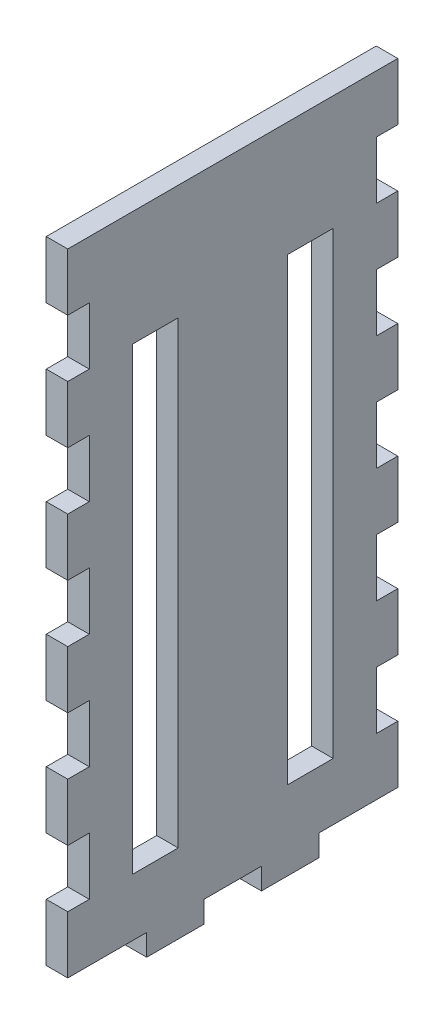
SolidWorks part; units mm, degrees
ref_plane "Front Plane" through (0, 0, 0) normal (0, 0, 1) x (1, 0, 0)
ref_plane "Top Plane" through (0, 0, 0) normal (0, 1, 0) x (1, 0, 0)
ref_plane "Right Plane" through (0, 0, 0) normal (1, 0, 0) x (0, 0, -1)
sketch "Sketch1" plane through (0, 0, 0) normal (1, 0, 0) x (0, 0, -1)
  line L1 (-63.5, -139.7) -> (63.5, -139.7)
  line L2 (-63.5, -139.7) -> (-63.5, 139.7)
  line L3 (-63.5, 139.7) -> (63.5, 139.7)
  line L4 (63.5, -139.7) -> (63.5, 139.7)
  line L5 (-63.5, -139.7) -> (63.5, 139.7) construction
  line L6 (-63.5, 139.7) -> (63.5, -139.7) construction
  point P0 (0, 0)
  dimension "D1" = 127
  dimension "D2" = 279.4
extrude "Boss-Extrude1" add sketch "Sketch1" along normal blind 9.525
sketch "Sketch2" plane through (0, 0, 63.5) normal (0, 0, 1) x (1, 0, 0)
  line L0 (0, 139.7) -> (0, -139.7) construction
  line L1 (0, 139.7) -> (9.525, 139.7)
  line L2 (0, 139.7) -> (0, 114.3)
  line L3 (0, 114.3) -> (9.525, 114.3)
  line L4 (9.525, 139.7) -> (9.525, 114.3)
  line L5 (0, -69.85) -> (0, 69.85) construction
  line L6 (9.525, 139.7) -> (9.525, -139.7) construction
  line L7 (9.525, 139.7) -> (0, 139.7) construction
  dimension "D1" = 25.4
  dimension "D2" = 0
extrude "Boss-Extrude2" add sketch "Sketch2" along normal blind 9.525
pattern_linear "LPattern1" count 6 spacing 50.8 along (0, -1, 0) of "Boss-Extrude2"
mirror "Mirror1" about plane through (0, 0, 0) normal (0, 0, 1) of "LPattern1"
sketch "Sketch3" plane through (0, -139.7, 0) normal (0, -1, 0) x (1, 0, 0)
  line L0 (0, 73.025) -> (0, -73.025) construction
  line L1 (0, 38.1) -> (9.525, 38.1)
  line L2 (0, 38.1) -> (0, 12.7)
  line L3 (0, 12.7) -> (9.525, 12.7)
  line L4 (9.525, 38.1) -> (9.525, 12.7)
  line L5 (9.525, 73.025) -> (9.525, -73.025) construction
  line L6 (0, 73.025) -> (9.525, 73.025) construction
  dimension "D1" = 34.925
  dimension "D2" = 25.4
extrude "Boss-Extrude3" add sketch "Sketch3" along normal blind 9.525
pattern_linear "LPattern2" count 2 spacing 50.8 along (0, 0, -1) of "Boss-Extrude3"
sketch "Sketch4" plane through (9.525, 0, 0) normal (1, 0, 0) x (0, 0, -1)
  line L1 (-44.45, -114.3) -> (-24.13, -114.3)
  line L3 (-44.45, 88.9) -> (-24.13, 88.9)
  line L5 (-73.025, -139.7) -> (-38.1, -139.7) construction
  line L6 (-73.025, 88.9) -> (-63.5, 88.9) construction
  line L7 (-24.13, -114.3) -> (-24.13, 88.9)
  line L8 (-44.45, -114.3) -> (-44.45, 88.9)
  line L9 (0, -139.7) -> (0, 139.7) construction
  line L10 (-12.7, -139.7) -> (12.7, -139.7) construction
  line L11 (73.025, 139.7) -> (-73.025, 139.7) construction
  point P10 (-68.2625, 88.9)
  dimension "D1" = 24.13
  dimension "D2" = 20.32
  dimension "D3" = 25.4
  dimension "D4" = 0
extrude "Cut-Extrude1" cut sketch "Sketch4" against normal blind 9.525
mirror "Mirror2" about plane through (0, 0, 0) normal (0, 0, 1) of "Cut-Extrude1"
sketch "Sketch5" plane through (0, 0, 0) normal (-1, 0, 0) x (0, 0, 1)
  circle A0 centre (-1.775, 53.4971) radius 2.5 construction
  circle A1 centre (-1.775, 53.4971) radius 2.5
  circle A2 centre (-1.775, 34.9971) radius 2.5 construction
  circle A3 centre (-1.775, 34.9971) radius 2.5
  circle A4 centre (1.775, 19.4611) radius 2.5 construction
  circle A5 centre (1.775, 19.4611) radius 2.5
  circle A6 centre (1.775, 0.9611) radius 2.5 construction
  circle A7 centre (1.775, 0.9611) radius 2.5
  circle A8 centre (-1.775, -16.5748) radius 2.5 construction
  circle A9 centre (-1.775, -16.5748) radius 2.5
  circle A10 centre (-1.775, -35.0748) radius 2.5 construction
  circle A11 centre (-1.775, -35.0748) radius 2.5
  circle A12 centre (1.775, -50.3148) radius 2.5 construction
  circle A13 centre (1.775, -50.3148) radius 2.5
  circle A14 centre (1.775, -68.8148) radius 2.5 construction
  circle A15 centre (1.775, -68.8148) radius 2.5
